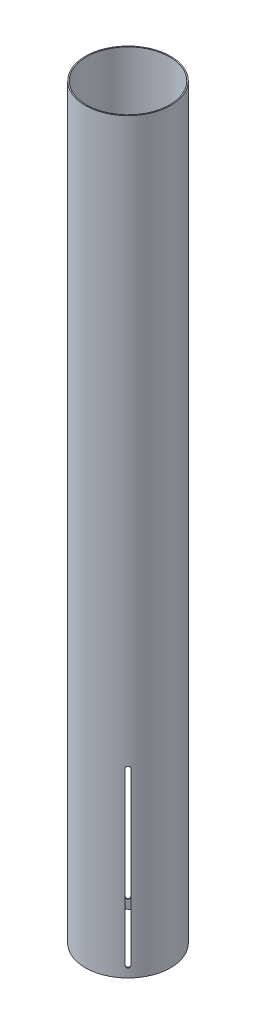
SolidWorks part; units mm, degrees
material "Wildman Fiberglass"
ref_plane "Front Plane" through (0, 0, 0) normal (0, 0, 1) x (1, 0, 0)
ref_plane "Top Plane" through (0, 0, 0) normal (0, 1, 0) x (1, 0, 0)
ref_plane "Right Plane" through (0, 0, 0) normal (1, 0, 0) x (0, 0, -1)
sketch "Sketch1" plane through (0, 0, 0) normal (0, 1, 0) x (1, 0, 0)
  circle A0 centre (0, 0) radius 49.53
  circle A1 centre (0, 0) radius 50.8
  dimension "D1" = 101.6
  dimension "D2" = 99.06
extrude "Boss-Extrude1" add sketch "Sketch1" along normal blind 889
extrude "Cut-Extrude1" cut sketch "Sketch2" against normal blind 152.4
sketch "Sketch2" plane through (1.0217, 1243.3556, -179.1581) normal (0.7071, 0, -0.7071) x (0, 1, 0)
  line L0 (-1230.6556, 128.3427) -> (-1027.4556, 128.3427)
  line L1 (-1027.4556, 123.5802) -> (-1230.6556, 123.5802)
  arc A0 (-1230.6556, 128.3427) -> (-1230.6556, 123.5802) centre (-1230.6556, 125.9615) ccw
  arc A1 (-1027.4556, 128.3427) -> (-1027.4556, 123.5802) centre (-1027.4556, 125.9615) cw
  point P6 (-1255.5364, 109.5647)
  point P7 (0, 0)
  point P8 (0, 0)
pattern_circular "CirPattern1" count 4 over 360 about axis through (0, 889, 0) along (0, -1, 0) of "Cut-Extrude1" reverse direction yes
equation "\"Length\"=35"
equation "\"D1@Boss-Extrude1\"=\"Length\""
